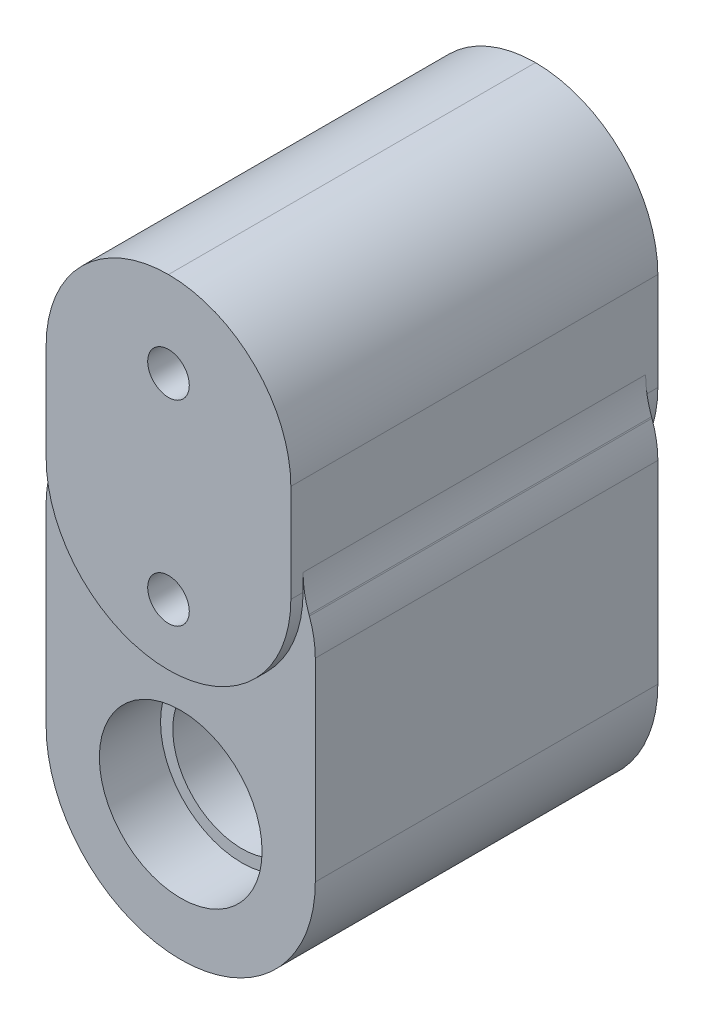
SolidWorks part; units mm, degrees
ref_plane "Спереди" through (0, 0, 0) normal (0, 0, 1) x (1, 0, 0)
ref_plane "Сверху" through (0, 0, 0) normal (0, 1, 0) x (1, 0, 0)
ref_plane "Справа" through (0, 0, 0) normal (1, 0, 0) x (0, 0, -1)
sketch "Эскиз1" plane through (0, 0, 0) normal (0, 0, 1) x (1, 0, 0)
  line L0 (0, 36) -> (0, -11) construction
  line L1 (-11, 38) -> (11, 38)
  line L2 (-11, 38) -> (-11, -11)
  line L3 (-11, -11) -> (11, -11)
  line L4 (11, 38) -> (11, -11)
  line L6 (-11, 0) -> (11, 0) construction
  dimension "D2" = 11
  dimension "D3" = 38
  dimension "D5" = 22
extrude "тело" add sketch "Эскиз1" along normal blind 14 and the other way blind 14
sketch "Эскиз2" plane through (0, 0, 14) normal (0, 0, 1) x (1, 0, 0)
  circle A0 centre (0, 0) radius 6.65
  dimension "D1" = 13.3
extrude "углубление для подшипника" cut sketch "Эскиз2" against normal blind 5
sketch "Эскиз4" plane through (0, 0, 9) normal (0, 0, 1) x (1, 0, 0)
  line L1 (0, 36) -> (0, -11) construction
  line L2 (-11, 0) -> (11, 0) construction
  circle A0 centre (0, 0) radius 5.65
  circle A1 centre (0, 0) radius 6.65 construction
  dimension "D1" = 1
extrude "сквозное отверстие" cut sketch "Эскиз4" against normal through all
mirror "Зеркальное отражение2" about plane through (0, 0, 0) normal (0, 0, 1) of "углубление для подшипника"
fillet "Скругление1" radius 11 2 edges at (11, -11, 0) (-11, -11, 0)
sketch "Эскиз5" plane through (0, 0, -14) normal (0, 0, -1) x (-1, 0, 0)
  line L0 (0, 38) -> (0, -11) construction
  line L1 (-11, 38) -> (11, 38) construction
  circle A0 centre (0, 31) radius 1.7
  circle A1 centre (0, 15) radius 1.7
  circle A2 centre (0, 0) radius 6.65 construction
  dimension "D1" = 3.4
  dimension "D2" = 16
  dimension "D3" = 15
extrude "отверстия под болты" cut sketch "Эскиз5" against normal through all
sketch "Эскиз9" plane through (0, 0, 14) normal (0, 0, 1) x (1, 0, 0)
  line L1 (-11, 10) -> (11, 10) construction
  line L2 (-10, 38) -> (10, 38)
  line L4 (-11, 38) -> (-11, 0) construction
  line L5 (11, 0) -> (11, 38) construction
  line L6 (-10, 20) -> (-10, 38)
  line L9 (10, 38) -> (10, 20)
  line L10 (11, 38) -> (-11, 38) construction
  arc A0 (-10, 20) -> (10, 20) centre (0, 20) ccw
  circle A1 centre (0, 15) radius 1.7
  circle A2 centre (0, 31) radius 1.7
  circle A3 centre (0, 31) radius 1.7 construction
  circle A5 centre (0, 15) radius 1.7 construction
  point P23 (0, 38)
  dimension "D1" = 10
  dimension "D2" = 5
  dimension "D3" = 20
extrude "выступы" add sketch "Эскиз9" along normal blind 1
mirror "Зеркальное отражение1" about plane through (0, 0, 0) normal (0, 0, 1) of "выступы"
sketch "Эскиз10" plane through (0, 0, 14) normal (0, 0, 1) x (1, 0, 0)
  line L0 (-10, 38) -> (-11, 38)
  line L1 (-11, 38) -> (-11, 17.2525)
  line L2 (-11, 38) -> (-11, 0) construction
  line L3 (0, 38) -> (0, 15) construction
  line L4 (-10, 38) -> (-10, 20)
  line L5 (-11, 17.2525) -> (-10, 20)
  line L6 (10, 38) -> (-10, 38) construction
  line L7 (11, 17.2525) -> (10, 20)
  line L8 (10, 38) -> (10, 20)
  line L9 (11, 38) -> (11, 17.2525)
  line L10 (10, 38) -> (11, 38)
  dimension "D1" = 20
extrude "Сглаживание перехода" cut sketch "Эскиз10" against normal up to next
fillet "Скругление2" radius 8 4 edges at (10, 20, 0) (11, 17.2525, 0) (-10, 20, 0) (-11, 17.2525, 0)
fillet "Скругление3" radius 10 2 edges at (-10, 38, 0) (10, 38, 0)
